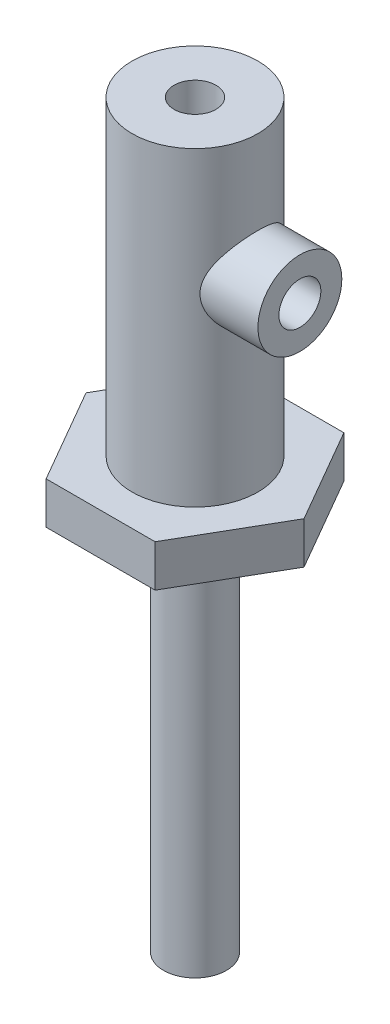
SolidWorks part; units mm, degrees
ref_plane "Front Plane" through (0, 0, 0) normal (0, 0, 1) x (1, 0, 0)
ref_plane "Top Plane" through (0, 0, 0) normal (0, 1, 0) x (1, 0, 0)
ref_plane "Right Plane" through (0, 0, 0) normal (1, 0, 0) x (0, 0, -1)
sketch "Sketch1" plane through (0, 0, 0) normal (0, 1, 0) x (1, 0, 0)
  circle A0 centre (0, 0) radius 3
  dimension "D1" = 6
extrude "Boss-Extrude1" add sketch "Sketch1" along normal blind 16.8
ref_plane "Plane1" through (0, 16.8, 0) normal (0, 1, 0) x (1, 0, 0)
ref_point "Point1"
sketch "Sketch2" plane through (0, 16.8, 0) normal (0, 1, 0) x (1, 0, 0)
  circle A0 centre (0, 0) radius 1
  dimension "D1" = 2
extrude "Cut-Extrude3" cut sketch "Sketch2" against normal blind 10.2
ref_plane "Plane2" through (0, 0, 0) normal (0, -1, 0) x (-1, 0, 0)
sketch "Sketch3" plane through (0, 0, 0) normal (0, -1, 0) x (-1, 0, 0)
  line L1 (5.1962, 0) -> (2.5981, 4.5)
  line L2 (2.5981, 4.5) -> (-2.5981, 4.5)
  line L3 (-2.5981, 4.5) -> (-5.1962, 0)
  line L4 (-5.1962, 0) -> (-2.5981, -4.5)
  line L5 (-2.5981, -4.5) -> (2.5981, -4.5)
  line L6 (2.5981, -4.5) -> (5.1962, 0)
  circle A0 centre (0, 0) radius 4.5 construction
  dimension "D1" = 9
extrude "Boss-Extrude2" add sketch "Sketch3" against normal blind 2
sketch "Sketch4" plane through (0, 0, 0) normal (0, -1, 0) x (-1, 0, 0)
  circle A0 centre (0, 0) radius 1.5
  dimension "D1" = 3
extrude "Boss-Extrude3" add sketch "Sketch4" along normal blind 18.5
ref_plane "Plane3" through (3, 0, 0) normal (1, 0, 0) x (0, 0, -1)
sketch "Sketch6" plane through (3, 0, 0) normal (1, 0, 0) x (0, 0, -1)
  line L0 (3.3, 16.8) -> (-3.3, 16.8) construction
  circle A0 centre (0, 10.8) radius 1
  circle A1 centre (0, 10.8) radius 2
  dimension "D2" = 2
  dimension "D3" = 4
  dimension "D1" = 6
extrude "Boss-Extrude4" add sketch "Sketch6" along normal blind 2 and the other way blind 1
ref_point "Point3"
sketch "Sketch7" plane through (3, 0, 0) normal (1, 0, 0) x (0, 0, -1)
  circle A0 centre (0, 10.8) radius 1.1
extrude "Cut-Extrude4" cut sketch "Sketch7" against normal blind 3
